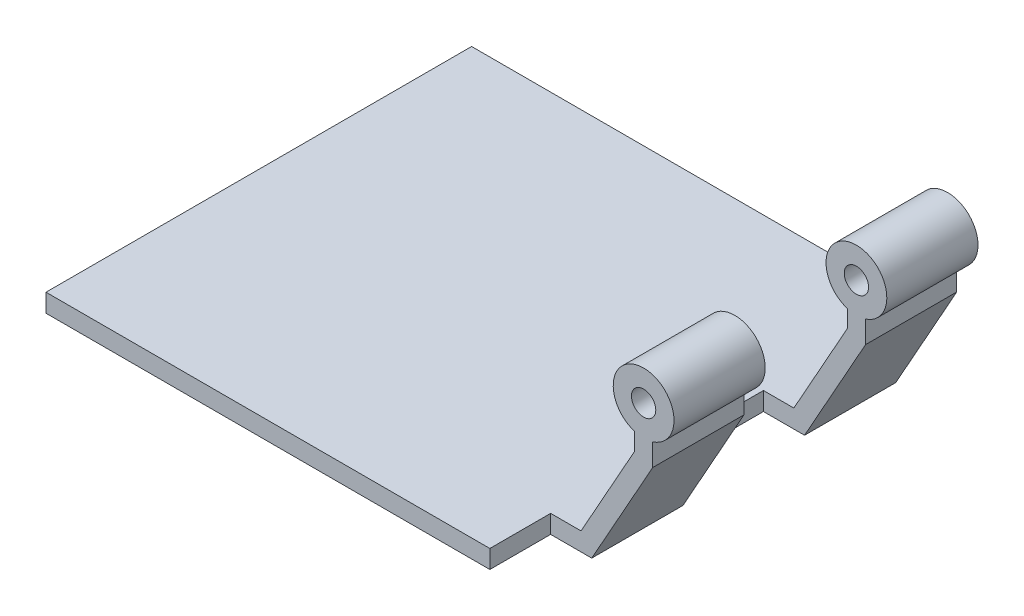
SolidWorks part; units mm, degrees
ref_plane "Front Plane" through (0, 0, 0) normal (0, 0, 1) x (1, 0, 0)
ref_plane "Top Plane" through (0, 0, 0) normal (0, 1, 0) x (1, 0, 0)
ref_plane "Right Plane" through (0, 0, 0) normal (1, 0, 0) x (0, 0, -1)
sketch "Sketch1" plane through (0, 0, 0) normal (0, 0, 1) x (1, 0, 0)
  line L0 (0, 3) -> (0, 0)
  line L1 (0, 0) -> (81.7588, 0)
  line L4 (88.7917, 18.7069) -> (80, 3)
  line L5 (80, 3) -> (0, 3)
  line L9 (81.7588, 0) -> (91.7917, 17.9244)
  line L11 (88.7917, 18.7069) -> (88.7917, 23.7069)
  line L12 (91.7917, 17.9244) -> (91.7917, 23.7069)
  line L13 (90.2917, 32.6026) -> (90.2917, 7.0815) construction
  line L14 (88.7917, 23.7069) -> (91.7917, 23.7069)
  circle A0 centre (90.2917, 26.3526) radius 5
  dimension "D9" = 10
  dimension "D1" = 80
  dimension "D2" = 3
  dimension "D3" = 18
  dimension "D4" = 3
  dimension "D5" = 119.237
  dimension "D6" = 5
  dimension "D7" = 3
  dimension "D8" = 1.5
extrude "Boss-Extrude1" add sketch "Sketch1" along normal blind 50 contours L9 L12 L14 L11 L4 L5 L0 L1 | A0
sketch "Sketch2" plane through (0, 0, 0) normal (0, 0, 1) x (1, 0, 0)
  circle A1 centre (90.2917, 26.3526) radius 2
  arc A2 (91.7917, 21.5829) -> (88.7917, 21.5829) centre (90.2917, 26.3526) ccw construction
  point P2 (88.697, 32.4609)
  point P11 (98.7108, 32.4609)
  point P12 (89.1184, 32.4609)
  point P13 (0, 0)
  point P14 (88.697, 32.4609)
  point P15 (88.697, 32.4609)
  dimension "D3" = 4
extrude "Cut-Extrude1" cut sketch "Sketch2" along normal through all
sketch "Sketch7" plane through (62.2541, -34.846, 0) normal (0.8726, -0.4884, 0) x (0, 0, -1)
  line L0 (-35, 89.9022) -> (-35, 28.0637) construction
  line L1 (-15, 89.9022) -> (-15, 25.2431) construction
  line L2 (-50, 39.9334) -> (-50, 60.4747) construction
  line L3 (0, 39.9334) -> (0, 60.4747) construction
  line L4 (-50, 39.9334) -> (0, 39.9334) construction
  line L5 (-35, 79.9206) -> (-15, 79.9206)
  line L6 (-35, 79.9206) -> (-35, 39.9334)
  line L7 (-35, 39.9334) -> (-15, 39.9334)
  line L8 (-15, 79.9206) -> (-15, 39.9334)
  point P6 (-35, 58.9829)
  dimension "D1" = 15
  dimension "D2" = 15
extrude "Cut-Extrude3" cut sketch "Sketch7" against normal blind 10 and the other way blind 10
sketch "Sketch8" plane through (0, 0, 0) normal (0, 0, 1) x (1, 0, 0)
  line L0 (66.951, 3) -> (66.951, 0)
  line L1 (80, 3) -> (0, 3) construction
  line L2 (0, 0) -> (81.7588, 0) construction
  line L3 (66.951, 0) -> (81.7588, 0)
  line L4 (81.7588, 0) -> (79.254, 1.6672)
  line L5 (88.7917, 18.7069) -> (80, 3) construction
  line L6 (79.254, 1.6672) -> (80, 3)
  line L7 (80, 3) -> (66.951, 3)
extrude "Boss-Extrude2" add sketch "Sketch8" along normal through all
sketch "Sketch9" plane through (0, 0, 0) normal (1, 0, 0) x (0, 0, -1)
  line L0 (-35, 21.5829) -> (-35, 31.3526) construction
  line L1 (-35, 37.4609) -> (-15, 37.4609)
  line L2 (-35, 37.4609) -> (-35, 26.5645)
  line L3 (-35, 26.5645) -> (-15, 26.5645)
  line L4 (-15, 37.4609) -> (-15, 26.5645)
  line L5 (-15, 17.9244) -> (-15, 21.5829) construction
extrude "Cut-Extrude4" cut sketch "Sketch9" along normal up to next
sketch "Sketch11" plane through (0, 0, 50) normal (0, 0, 1) x (1, 0, 0)
  line L0 (80, 3) -> (0, 3) construction
  line L1 (0, 0) -> (5, 0)
  line L2 (0, 0) -> (0, 3)
  line L3 (0, 3) -> (5, 3)
  line L4 (5, 0) -> (5, 3)
  point P7 (5, 1.5)
  dimension "D1" = 5
extrude "Cut-Extrude6" cut sketch "Sketch11" against normal up to body separate body
sketch "Sketch12" plane through (0, 3, 0) normal (0, 1, 0) x (1, 0, 0)
  line L0 (80, -15) -> (80, 0) construction
  line L1 (2, 10) -> (75, 10)
  line L2 (2, 10) -> (2, -60)
  line L3 (2, -60) -> (75, -60)
  line L4 (75, 10) -> (75, -60)
  line L6 (80, 0) -> (5, 0) construction
  line L7 (80, -50) -> (5, -50) construction
  line L8 (5, 0) -> (5, -50) construction
  dimension "D1" = 5
  dimension "D2" = 10
  dimension "D3" = 10
  dimension "D4" = 3
extrude "Boss-Extrude3" add sketch "Sketch12" against normal through all
sketch "Sketch13" plane through (0, 3, 0) normal (0, 1, 0) x (1, 0, 0)
  line L0 (75, 0) -> (75, -50) construction
  line L1 (81.7588, -15) -> (75, -15) construction
  line L2 (81.7588, -35) -> (75, -35) construction
  line L4 (75, -15) -> (81.7588, -15)
  line L5 (75, -15) -> (75, -35)
  line L6 (75, -35) -> (81.7588, -35)
  line L7 (81.7588, -15) -> (81.7588, -35)
extrude "Cut-Extrude7" cut sketch "Sketch13" against normal through all
